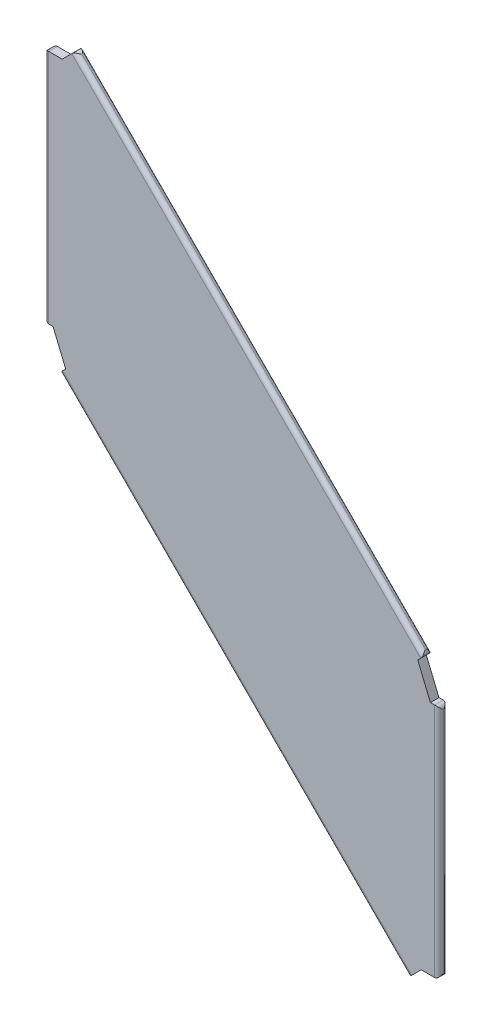
SolidWorks part; units mm, degrees
ref_plane "前视基准面" through (0, 0, 0) normal (0, 0, 1) x (1, 0, 0)
ref_plane "上视基准面" through (0, 0, 0) normal (0, 1, 0) x (1, 0, 0)
ref_plane "右视基准面" through (0, 0, 0) normal (1, 0, 0) x (0, 0, -1)
sketch "草图1" plane through (0, 0, 0) normal (0, 0, 1) x (1, 0, 0)
  line L31 (0, 0) -> (0, -7)
  line L32 (0, 0) -> (-9.1924, 9.1924)
  line L33 (0, -7) -> (-9.1924, 2.1924)
  line L34 (-9.1924, 9.1924) -> (-9.1924, 2.1924)
  line L35 (0, -6) -> (-0.4142, -6)
  line L36 (-0.4142, -6) -> (-0.7071, -6.2929)
  line L37 (-0.3536, 0.3536) -> (-0.495, 0.2121)
  line L38 (-0.2, -0.5) -> (0, -0.5)
  line L39 (-0.495, 0.2121) -> (-0.2, -0.5)
  line L40 (-8.4853, 8.4853) -> (-8.7782, 8.1924)
  line L41 (-8.7782, 8.1924) -> (-9.1924, 8.1924)
  line L42 (-9.1924, 2.6924) -> (-8.9924, 2.6924)
  line L43 (-8.6974, 1.9803) -> (-8.8388, 1.8388)
  line L44 (-8.9924, 2.6924) -> (-8.6974, 1.9803)
  dimension "D2" = 13
  dimension "D1" = 7
  dimension "D3" = 45
  dimension "D4" = 1
  dimension "D5" = 1
  dimension "D6" = 0.5
  dimension "D7" = 0.5
  dimension "D8" = 0.2
  dimension "D9" = 0.2
  dimension "D10" = 1
  dimension "D11" = 1
  dimension "D12" = 0.5
  dimension "D13" = 0.5
  dimension "D14" = 0.2
  dimension "D15" = 0.2
extrude "凸台-拉伸1" add sketch "草图1" along normal blind 0.2 contours L42 L44 L43 L33 L36 L35 L31 L38 L39 L37 L32 L40 L41 L34 region at (-4.5962, 1.0962, 0)
fillet "圆角1" radius 0.1 16 edges at (0, -6, 0.1) (0, -3.25, 0.2) (0, -0.5, 0.1) (0, -3.25, 0) (-8.8388, 1.8388, 0.1) (-4.773, -2.227, 0.2) (-0.7071, -6.2929, 0.1) (-4.773, -2.227, 0) (-9.1924, 8.1924, 0.1) (-9.1924, 5.4424, 0.2) (-9.1924, 2.6924, 0.1) (-9.1924, 5.4424, 0) (-0.3536, 0.3536, 0.1) (-4.4194, 4.4194, 0.2) (-8.4853, 8.4853, 0.1) (-4.4194, 4.4194, 0)
